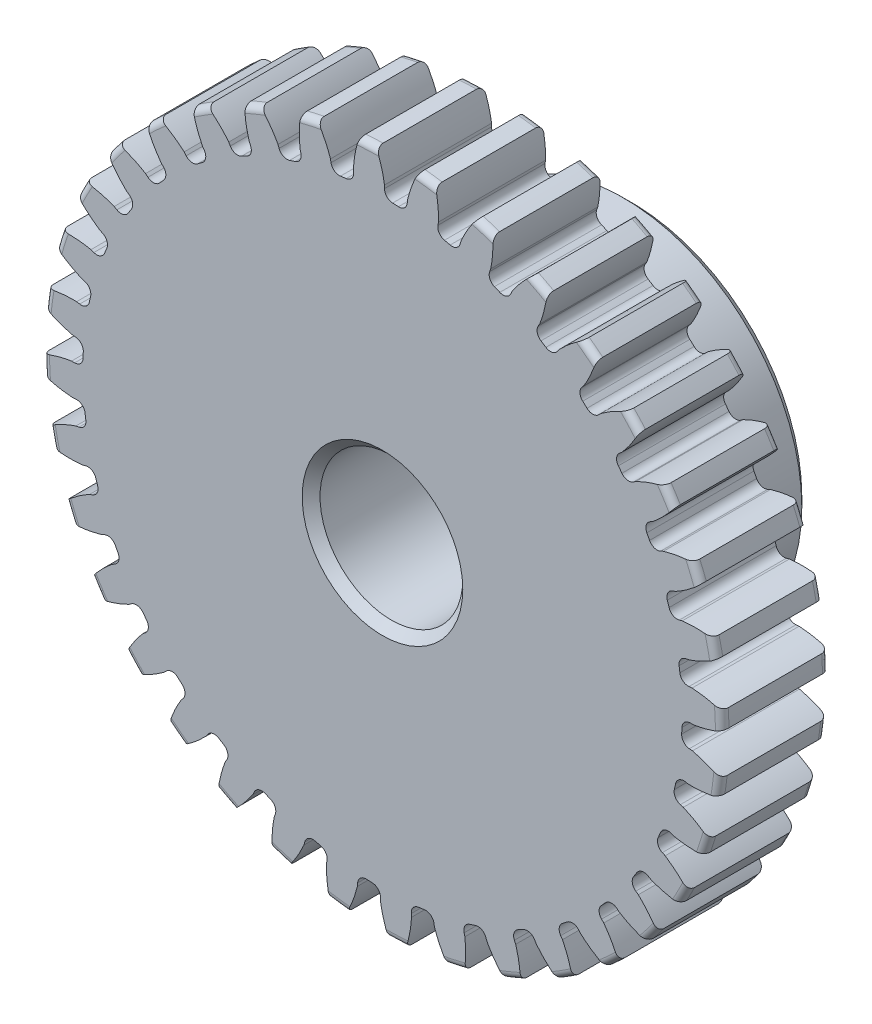
SolidWorks part; units mm, degrees
ref_plane "Front" through (0, 0, 0) normal (0, 0, 1) x (1, 0, 0)
ref_plane "Top" through (0, 0, 0) normal (0, 1, 0) x (1, 0, 0)
ref_plane "Right" through (0, 0, 0) normal (1, 0, 0) x (0, 0, -1)
sketch "Sketch1" plane through (0, 0, 0) normal (0, 0, 1) x (1, 0, 0)
  line L0 (-457.2, 0) -> (457.2, 0) construction
  circle A0 centre (0, 0) radius 15.113
  circle A1 centre (0, 0) radius 14.2875 construction
  circle A3 centre (0, 0) radius 13.3271 construction
  dimension "D1" = 1.7859
  dimension "OD" = 30.226
  dimension "Ptich Dia" = 28.575
  dimension "Root Dia" = 26.6541
  dimension "D3" = 0.8255
  dimension "Number of Teeth" = 914.4
extrude "Boss-Extrude1" add sketch "Sketch1" against normal blind 4.7625
sketch "Sketch2" plane through (0, 0, 0) normal (1, 0, 0) x (0, 0, -1)
  line L0 (4.7625, 0) -> (11.1125, 0)
  line L1 (4.7625, 0) -> (4.7625, 7.9375)
  line L2 (4.7625, 7.9375) -> (11.1125, 7.9375)
  line L3 (11.1125, 7.9375) -> (11.1125, 0)
  point P5 (11.1125, -7.9375)
  point P6 (0, -15.113)
  point P7 (4.7625, -15.113)
  point P9 (0, 15.113)
  dimension "Face Wd" = 4.7625
  dimension "B Hub Dia" = 15.875
  dimension "D O'all Lg." = 11.1125
revolve "Revolve1" add sketch "Sketch2" angle 360 mid plane about L0
fillet "Fillet2" radius 0.3023 3 edges at (15.113, 0, -4.7625) (15.113, 0, 0) (7.9375, 0, -4.7625)
sketch "Sketch3" plane through (0, 0, 0) normal (0, 0, 1) x (1, 0, 0)
  line L0 (0, 0) -> (0, 15.113) construction
  line L1 (-3.4634, 13.3918) -> (0, 14.2875)
  line L2 (-9.5921, 14.2875) -> (9.5921, 14.2875) construction
  line L3 (-9.2865, 11.8858) -> (9.2865, 16.6892) construction
  line L4 (-3.4634, 13.3918) -> (0, 0) construction
  line L5 (-8.8339, 10.6442) -> (0, 0) construction
  line L6 (-8.8339, 10.6442) -> (-1.4209, 16.7964) construction
  line L7 (-2.415, 13.62) -> (0, 0) construction
  line L8 (-2.415, 13.62) -> (0.0507, 14.0572) construction
  arc A0 (-3.4634, 13.3918) -> (-8.8339, 10.6442) centre (0, 0) ccw
  circle A1 centre (0, 0) radius 14.2875 construction
  circle A2 centre (0, 0) radius 13.8324 construction
  arc A3 (-3.4634, 13.3918) -> (-2.415, 13.62) centre (0, 0) cw
  circle A4 centre (0, 0) radius 15.113 construction
  point P6 (0, 14.2875)
  dimension "D1" = 3.5773
  dimension "Pressure Angle" = 14.5
  dimension "D2" = 6.0814
  dimension "D3" = 9.6333
  dimension "D4" = 1.0732
  dimension "D5" = 2.5041
sketch "Sketch4" plane through (0, 0, 0) normal (0, 0, 1) x (1, 0, 0)
  line L0 (0, 0) -> (0.6226, 14.2603) construction
  line L1 (0.0898, 13.8321) -> (0.0898, 13.3268)
  line L2 (0, 14.2875) -> (1.2452, 14.2331) construction
  line L3 (1.1161, 13.7873) -> (1.072, 13.2839)
  line L4 (0.0898, 13.3268) -> (0, 0) construction
  line L5 (0, 0) -> (0, 15.113) construction
  line L6 (-8.8339, 10.6442) -> (-1.4209, 16.7964) construction
  line L7 (-8.8339, 10.6442) -> (-1.4209, 16.7964) construction
  arc A0 (1.072, 13.2839) -> (0.0898, 13.3268) centre (0, 0) ccw
  arc A1 (0, 14.2875) -> (1.2452, 14.2331) centre (0, 0) cw construction
  circle A2 centre (0, 0) radius 14.2875 construction
  circle A3 centre (0, 0) radius 13.8324 construction
  circle A4 centre (0, 0) radius 13.3271 construction
  arc A5 (2.8794, 16.6086) -> (-1.4209, 16.7964) centre (0, 0) ccw
  spline S0 degree 2 poles (-1.4209, 16.7964) (-0.1618, 15.4883) (0.0898, 13.8321) knots 0 0 0 1 1 1
  spline S1 degree 2 poles (2.8794, 16.6086) (1.5111, 15.4152) (1.1161, 13.7873) knots 0 0 0 1 1 1
  dimension "D1" = 1.2468
extrude "Cut-Extrude1" cut sketch "Sketch4" against normal through all
fillet "Fillet1" radius 0.374 2 edges at (1.072, 13.2839, -2.3813) (0.0898, 13.3268, -2.3813)
pattern_circular "CirPattern1" count 36 over 360 about axis through (0, 0, -4.7625) along (0, 0, 1) of "Cut-Extrude1", "Fillet1"
sketch "Sketch5" plane through (0, 0, 0) normal (0, 0, 1) x (1, 0, 0)
  circle A0 centre (0, 0) radius 3.175
  circle A1 centre (0, 0) radius 1.5875 construction
  dimension "Bore Min" = 6.35
  dimension "Bore Max" = 3.175
extrude "Cut-Extrude2" cut sketch "Sketch5" against normal through all
chamfer "Chamfer1" distance 0.3969 angle 45 3 edges at (7.9375, 0, -11.1125) (3.175, 0, 0) (3.175, 0, -11.1125)
sketch "Pitch Dia" plane through (0, 0, 0) normal (0, 0, 1) x (1, 0, 0)
  circle A0 centre (0, 0) radius 14.2875 construction
  circle A1 centre (0, 0) radius 14.2875 construction
equation "\"D1@Boss-Extrude1\" = \"Face Wd@Sketch2\""
equation "\"D2@Sketch3\" = \"D1@Sketch3\"*1.7"
equation "\"D3@Sketch3\" = \"D1@Sketch3\"+\"D2@Sketch3\"-.001"
equation "\"D4@Sketch3\" = \"D1@Sketch3\"*.3"
equation "\"D5@Sketch3\" = \"D1@Sketch3\"-\"D4@Sketch3\""
equation "\"D1@Sketch4\" = 1.5708/(\"Number of Teeth@Sketch1\"/\"Ptich Dia@Sketch1\")"
equation "\"D1@Chamfer1\" = \"B Hub Dia@Sketch2\"*.025"
equation "\"D1@CirPattern1\" = \"Number of Teeth@Sketch1\""
equation "\"D1@Fillet1\" = \"D1@Sketch4\"*.3"
equation "\"D1@Fillet2\" = \"OD@Sketch1\"*.01"
equation "\"D1@Sketch1\" = 2.250/(\"Number of Teeth@Sketch1\"/\"Ptich Dia@Sketch1\")"
